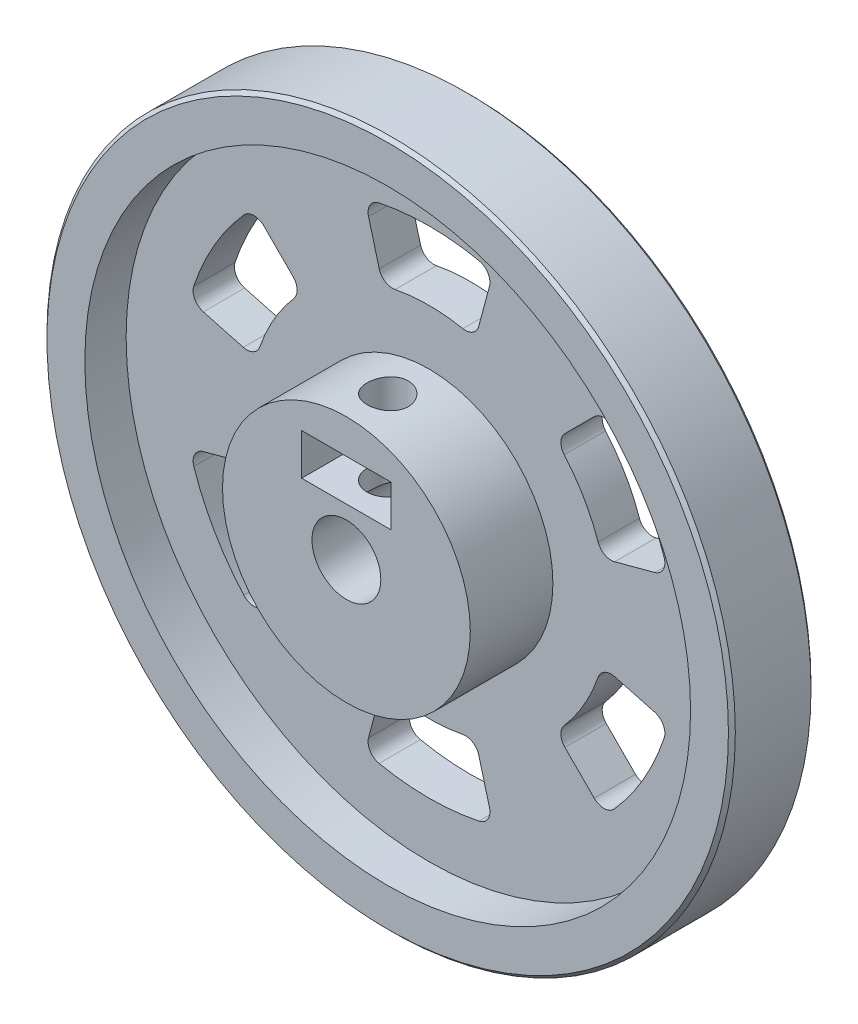
SolidWorks part; units mm, degrees
material "ABS"
ref_plane "Front Plane" through (0, 0, 0) normal (0, 0, 1) x (1, 0, 0)
ref_plane "Top Plane" through (0, 0, 0) normal (0, 1, 0) x (1, 0, 0)
ref_plane "Right Plane" through (0, 0, 0) normal (1, 0, 0) x (0, 0, -1)
sketch "Sketch1" plane through (0, 0, 0) normal (0, 0, 1) x (1, 0, 0)
  circle A0 centre (0, 0) radius 25
  dimension "D1" = 50
extrude "Boss-Extrude1" add sketch "Sketch1" along normal blind 3
sketch "Sketch3" plane through (0, 0, 0) normal (0, 0, 1) x (1, 0, 0)
  circle A0 centre (0, 0) radius 22
  circle A1 centre (0, 0) radius 25 construction
  circle A2 centre (0, 0) radius 25
  dimension "D1" = 3
extrude "Boss-Extrude3" add sketch "Sketch3" along normal blind 6
sketch "Sketch4" plane through (0, 0, 0) normal (0, 0, 1) x (1, 0, 0)
  circle A0 centre (0, 0) radius 9
  dimension "D1" = 18
extrude "Boss-Extrude4" add sketch "Sketch4" along normal blind 9
sketch "Sketch5" plane through (0, 0, 0) normal (0, 0, 1) x (1, 0, 0)
  circle A0 centre (0, 0) radius 2.5
  dimension "D1" = 5
extrude "Cut-Extrude1" cut sketch "Sketch5" along normal through all
sketch "Sketch6" plane through (0, 0, 9) normal (0, 0, 1) x (1, 0, 0)
  line L0 (0, 5) -> (0, 0) construction
  line L1 (-3.25, 6.5) -> (3.25, 6.5)
  line L2 (-3.25, 6.5) -> (-3.25, 3.5)
  line L3 (-3.25, 3.5) -> (3.25, 3.5)
  line L4 (3.25, 6.5) -> (3.25, 3.5)
  line L5 (-3.25, 6.5) -> (3.25, 3.5) construction
  line L6 (-3.25, 3.5) -> (3.25, 6.5) construction
  point P0 (0, 5)
  dimension "D1" = 3
  dimension "D2" = 6.5
  dimension "D3" = 5
extrude "Cut-Extrude2" cut sketch "Sketch6" against normal blind 6.5
sketch "Sketch7" plane through (0, 0, 0) normal (0, 1, 0) x (1, 0, 0)
  line L0 (0, 0) -> (0, -6) construction
  line L1 (3.25, -9) -> (-3.25, -9) construction
  circle A0 centre (0, -6) radius 1.5
  point P3 (0, -9)
  dimension "D2" = 3
  dimension "D1" = 3
extrude "Cut-Extrude3" cut sketch "Sketch7" along normal up to surface (9 mm away) up to face at (9, 0, 3)
sketch "Sketch8" plane through (0, 0, 0) normal (0, 0, 1) x (1, 0, 0)
  line L0 (0, 22) -> (0, 9) construction
  line L1 (0, 0) -> (-5.694, 21.2504) construction
  line L2 (-4.3923, 16.3923) -> (-3.6142, 13.4884)
  line L3 (0, 18) -> (0, 13) construction
  line L4 (4.3923, 16.3923) -> (3.6142, 13.4884)
  arc A0 (-3.6279, 17.6306) -> (3.6279, 17.6306) centre (0, 0) cw
  circle A1 centre (0, 0) radius 22 construction
  circle A2 centre (0, 0) radius 22 construction
  circle A3 centre (0, 0) radius 9 construction
  arc A4 (-2.4591, 12.7653) -> (2.4591, 12.7653) centre (0, 0) cw
  arc A5 (-2.4591, 12.7653) -> (-3.6142, 13.4884) centre (-2.6483, 13.7472) cw
  arc A6 (-3.6279, 17.6306) -> (-4.3923, 16.3923) centre (-3.4264, 16.6511) ccw
  arc A7 (2.4591, 12.7653) -> (3.6142, 13.4884) centre (2.6483, 13.7472) ccw
  arc A8 (3.6279, 17.6306) -> (4.3923, 16.3923) centre (3.4264, 16.6511) cw
  point P11 (0, 15.5)
  point P19 (-3.3646, 12.557)
  point P22 (-4.6587, 17.3867)
  point P23 (0, 15.5)
  dimension "D1" = 1
  dimension "D2" = 4
  dimension "D3" = 15
extrude "Cut-Extrude4" cut sketch "Sketch8" along normal through all
pattern_circular "CirPattern1" count 6 over 360 about axis through (0, 0, 9) along (0, 0, 1) of "Cut-Extrude4"
chamfer "Chamfer1" distance 0.25 angle 45 2 edges at (25, 0, 6) (25, 0, 0)
ref_plane "Plane1" through (0, 0, 3) normal (0, 0, 1) x (1, 0, 0)
